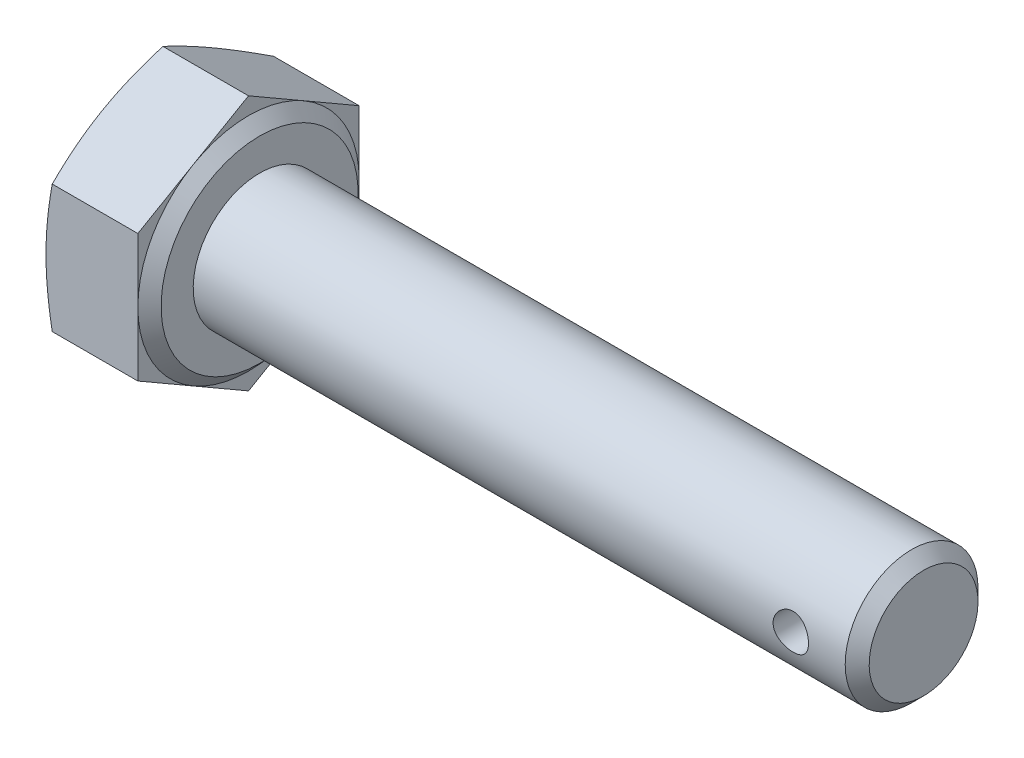
SolidWorks part; units mm, degrees
ref_plane "Front" through (0, 0, 0) normal (0, 0, 1) x (1, 0, 0)
ref_plane "Top" through (0, 0, 0) normal (0, 1, 0) x (1, 0, 0)
ref_plane "Right" through (0, 0, 0) normal (1, 0, 0) x (0, 0, -1)
sketch "Sketch-BaseHead" plane through (0, 0, 0) normal (1, 0, 0) x (0, 0, -1)
  line L1 (0, -5.7735) -> (5, -2.8868)
  line L2 (5, -2.8868) -> (5, 2.8868)
  line L3 (5, 2.8868) -> (0, 5.7735)
  line L4 (0, 5.7735) -> (-5, 2.8868)
  line L5 (-5, 2.8868) -> (-5, -2.8868)
  line L6 (-5, -2.8868) -> (0, -5.7735)
  circle A0 centre (0, 0) radius 5 construction
extrude "BaseHead" add sketch "Sketch-BaseHead" along normal blind 4.15
sketch "Sketch4" plane through (-0.2646, -5.9169, 0) normal (0, 0, 1) x (0, 1, 0)
  line L0 (5.9169, 3.7369) -> (5.9169, -10.4477) construction
  line L2 (11.6904, -0.2646) -> (10.9169, -0.2646)
  line L4 (10.9169, -0.2646) -> (11.6904, -0.5462)
  line L6 (11.6904, -0.5462) -> (11.6904, -0.2646)
  dimension "D1" = 20
  dimension "D2" = 10
revolve "HeadChamfer" cut sketch "Sketch4" angle 360 about L0
sketch "Sketch1" plane through (0, 0, 0) normal (0, 1, 0) x (1, 0, 0)
  line L0 (4.15, 0) -> (4.65, 0)
  line L1 (4.65, 0) -> (4.65, 4.45)
  line L2 (4.65, 4.45) -> (4.15, 5)
  line L3 (4.15, 5) -> (4.15, 0)
  line L6 (-4.0016, 0) -> (10.1831, 0) construction
  dimension "D1" = 5
  dimension "D2" = 4.45
  dimension "D3" = 0.5
revolve "Revolve1" add sketch "Sketch1" angle 360 about axis through (-4.0016, 0, 0) along (1, 0, 0)
ref_plane "Plane2" through (16.65, 0, 0) normal (1, 0, 0) x (0, 0, -1)
sketch "Sketch3" plane through (4.65, 0, 0) normal (1, 0, 0) x (0, 0, -1)
  circle A0 centre (0, 0) radius 3
extrude "BaseBody" add sketch "Sketch3" along normal blind 30
cosmetic thread "ThreadCosmetic1" [suppressed] parameters "b"=18, "D2"=4.917
chamfer "Chamfer1" distance 0.5415 angle 45 1 edges at (34.65, 3, 0)
fillet "HeadFillet" [suppressed] radius 0.25
sketch "Sketch5" plane through (0, 0, 0) normal (0, 0, 1) x (1, 0, 0)
  line L2 (4.65, -4.45) -> (4.65, 4.45) construction
  line L3 (34.1085, 0) -> (4.65, 0) construction
  circle A0 centre (31.65, 0) radius 0.8
  dimension "d1" = 1.6
  dimension "lh" = 27
extrude "Hole" cut sketch "Sketch5" against normal through all and the other way through all
sketch "Sketch6" plane through (0, 0, 0) normal (0, 0, 1) x (1, 0, 0)
  line L0 (33.566, 3.2) -> (34.1075, 3.2)
  line L1 (34.1075, 3.2) -> (34.1075, 3)
  line L2 (34.1075, 3) -> (33.8367, 2.531)
  line L3 (33.566, 3) -> (33.8367, 2.531)
  line L4 (33.566, 3.2) -> (33.566, 3)
  line L5 (27.8988, 0) -> (0, 0) construction
  line L6 (33.566, 3) -> (34.1075, 3) construction
  line L7 (33.8367, 3) -> (33.8367, 2.531) construction
  line L8 (34.1085, 3) -> (4.65, 3) construction
  point P5 (33.8367, 3.2)
  dimension "D2" = 0.5415
revolve "Cut-Revolve10" [suppressed] cut sketch "Sketch6" angle 360 about L5
pattern_linear "LPattern10" [suppressed] count 28 spacing 0.6498 of bodies 110
equation "\"D1@Sketch1\" = \"s@Sketch-BaseHead\" / 2"
equation "\"D2@Sketch4\" = \"s@Sketch-BaseHead\""
equation "\"D1@Chamfer1\" = (  \"d@Sketch3\"  -\"D2@ThreadCosmetic1\" ) / 2 "
equation "\"b@ThreadCosmetic1\" = \"l@BaseBody\" - \"lg@Plane2\""
equation "\"D2@Sketch6\" = (  \"d@Sketch3\" - \"D2@ThreadCosmetic1\" )  / 2"
equation "\"D3@LPattern10\" =\"D2@Sketch6\" * 1.2"
equation "\"D1@LPattern10\" = \"b@ThreadCosmetic1\" / \"D3@LPattern10\""
equation "\"D3@Sketch6\" = 0.001"
